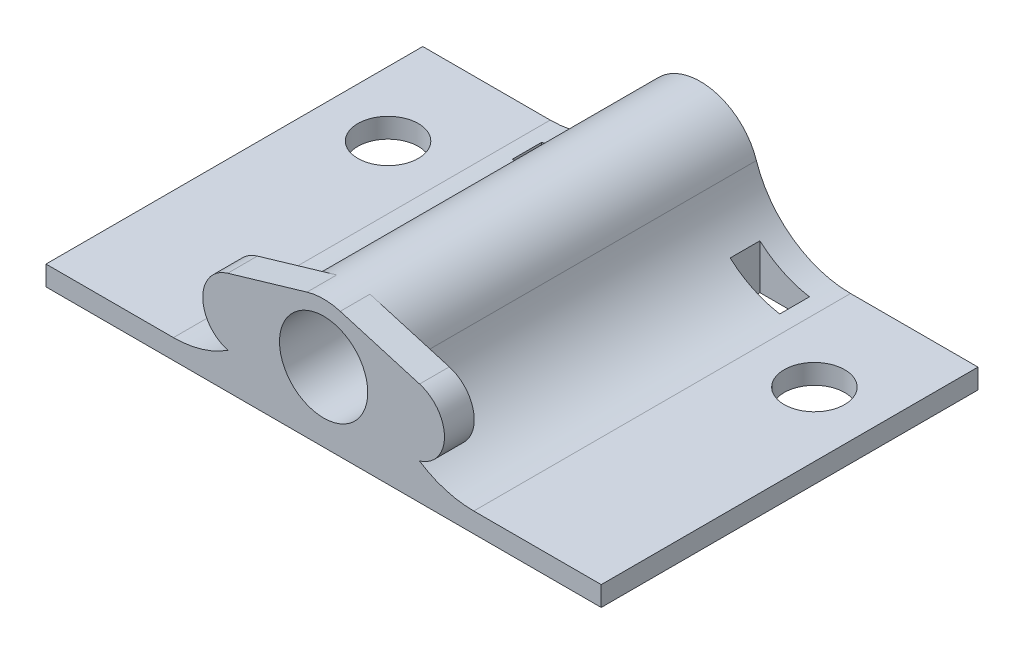
SolidWorks part; units mm, degrees
note: The reader was unsure of these and kept them because the rebuilt part matched: shared geometry of "Esquisse1<2>".
ref_plane "Plan de face" through (0, 0, 0) normal (0, 0, 1) x (1, 0, 0)
ref_plane "Plan de dessus" through (0, 0, 0) normal (0, 1, 0) x (1, 0, 0)
ref_plane "Plan de droite" through (0, 0, 0) normal (1, 0, 0) x (0, 0, -1)
sketch "Esquisse1" plane through (0, 0, 0) normal (0, 0, 1) x (1, 0, 0)
  line L0 (-2, 3.5) -> (2, -3.5) construction
  line L1 (-2, 3.5) -> (2, 3.5) construction
  line L2 (-2, 3.5) -> (-2, -3.5) construction
  line L3 (-2, -3.5) -> (2, -3.5) construction
  line L4 (2, 3.5) -> (2, -3.5) construction
  circle A0 centre (0, 0) radius 4.45
  point P7 (0, 0)
  point P8 (0, 3.5)
  dimension "D1" = 8.9
  dimension "D2" = 7
  dimension "D3" = 4
extrude "Boss.-Extru.1" add sketch "Esquisse1" along normal blind 1.5
extrude "Extru.-Mince1" add sketch "Esquisse1<2>" along normal blind 35 thin contours A0
sketch "Esquisse1<2>" plane through (0, 0, 0) normal (0, 0, 1) x (1, 0, 0) same geometry as "Esquisse1"
sketch "Esquisse2" plane through (0, 0, 35) normal (0, 0, 1) x (1, 0, 0)
  line L0 (-1.6774, 5.7087) -> (-9.6774, 3.358)
  line L1 (-4.45, 0) -> (4.45, 0) construction
  line L6 (0, -4.45) -> (0, 4.45) construction
  line L8 (-1.6774, -5.7087) -> (-9.6774, -3.358)
  line L9 (1.6774, -5.7087) -> (9.6774, -3.358)
  line L10 (1.6774, 5.7087) -> (9.6774, 3.358)
  circle A0 centre (0, 0) radius 5.95 construction
  arc A1 (-9.6774, 3.358) -> (-12.1907, 0) centre (-8.6907, 0) ccw
  arc A2 (-9.6774, -3.358) -> (-12.1907, 0) centre (-8.6907, 0) cw
  arc A3 (9.6774, -3.358) -> (12.1907, 0) centre (8.6907, 0) ccw
  arc A4 (9.6774, 3.358) -> (12.1907, 0) centre (8.6907, 0) cw
  circle A5 centre (0, 0) radius 4.45 construction
  circle A6 centre (0, 0) radius 4.45
  circle A7 centre (0, 0) radius 5.95
  circle M5 centre (0, 0) radius 5.95
  circle M6 centre (0, 0) radius 4.45
  dimension "D1" = 8
  dimension "D2" = 3.5
extrude "Boss.-Extru.2" add sketch "Esquisse2" along normal blind 3 contours A4 L10 L9 A3 M5 | A2 L8 L0 A1 M5 | M5 M6 | A6
ref_plane "Plan1" through (0, -5, 0) normal (0, 1, 0) x (1, 0, 0)
sketch "Esquisse4" plane through (0, -5, 0) normal (0, 1, 0) x (1, 0, 0)
  line L0 (5.95, 0) -> (-5.95, 0) construction
  line L1 (-28, 0) -> (28, 0)
  line L2 (-28, 0) -> (-28, -38)
  line L5 (0, 0) -> (0, -169.7294) construction
  line L7 (1.6774, -38) -> (9.6774, -38) construction
  line L10 (-28, -38) -> (28, -38)
  line L12 (28, 0) -> (28, -38)
  circle A0 centre (-21.5, -10) radius 3.05
  circle A4 centre (21.5, -10) radius 3.05
  dimension "D3" = 6.1
  dimension "D4" = 6.5
  dimension "D5" = 10
  dimension "D1" = 28
extrude "Boss.-Extru.3" add sketch "Esquisse4" against normal blind 2
fillet "Congé1" radius 10 6 edges at (-3.2253, -5, 17.5) (3.2253, -5, 17.5) (4.0892, -5, 36.5) (3.6573, -5, 35) (-3.6573, -5, 35) (-4.0892, -5, 36.5)
sketch "Esquisse5" plane through (0, 0, 0) normal (0, 0, -1) x (-1, 0, 0)
  circle A0 centre (0, 0) radius 4.45 construction
  circle A1 centre (0, 0) radius 4.45
extrude "Enlèv. mat.-Extru.1" cut sketch "Esquisse5" against normal blind 10
sketch "Esquisse8" plane through (0, -5, 0) normal (0, 1, 0) x (1, 0, 0)
  line L0 (0, 9.5182) -> (0, -32.3497) construction
  line L1 (-13.5, -2.5) -> (-8.5, -2.5)
  line L2 (-13.5, -2.5) -> (-13.5, -5.5)
  line L3 (-13.5, -5.5) -> (-8.5, -5.5)
  line L4 (-8.5, -2.5) -> (-8.5, -5.5)
  line L5 (8.5, -2.5) -> (8.5, -5.5)
  line L6 (13.5, -5.5) -> (8.5, -5.5)
  line L7 (13.5, -2.5) -> (13.5, -5.5)
  line L8 (13.5, -2.5) -> (8.5, -2.5)
  line L10 (-28, 0) -> (28, 0) construction
  dimension "D1" = 5
  dimension "D2" = 3
  dimension "D3" = 8.5
  dimension "D4" = 2.5
extrude "Enlèv. mat.-Extru.4" cut sketch "Esquisse8" against normal through all both and the other way through all
